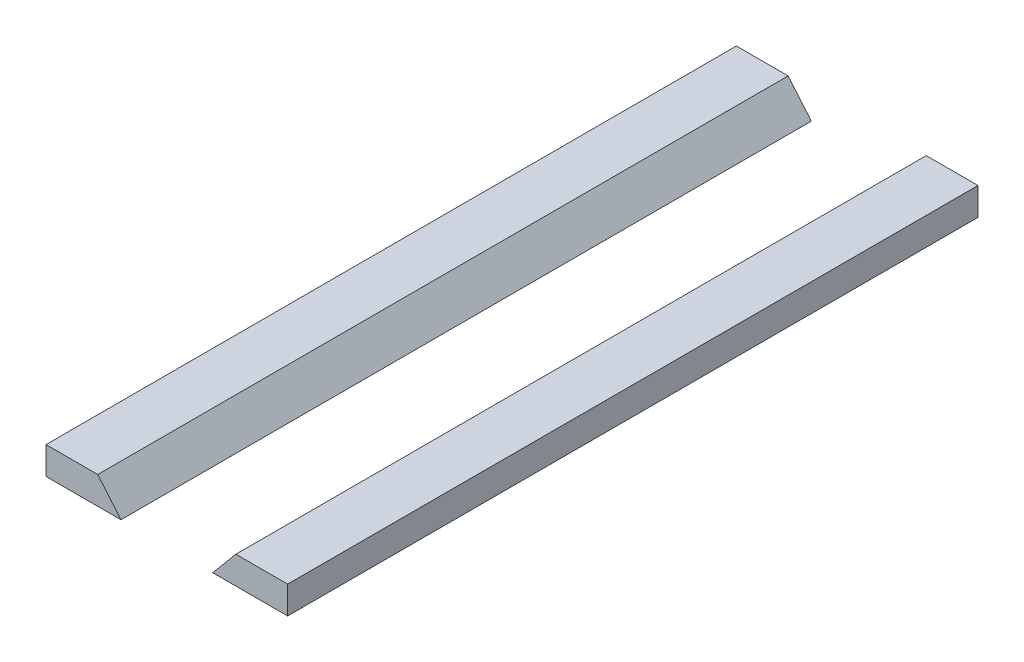
SolidWorks part; units mm, degrees
ref_plane "Płaszczyzna przednia" through (0, 0, 0) normal (0, 0, 1) x (1, 0, 0)
ref_plane "Płaszczyzna górna" through (0, 0, 0) normal (0, 1, 0) x (1, 0, 0)
ref_plane "Płaszczyzna prawa" through (0, 0, 0) normal (1, 0, 0) x (0, 0, -1)
sketch "Szkic1" plane through (0, 0, 0) normal (0, 0, 1) x (1, 0, 0)
  line L0 (-10, 2) -> (-6.6436, -2)
  line L1 (-17.5, 2) -> (17.5, 2)
  line L2 (-17.5, 2) -> (-17.5, -2)
  line L3 (-17.5, -2) -> (17.5, -2)
  line L4 (17.5, 2) -> (17.5, -2)
  line L5 (-17.5, 2) -> (17.5, -2) construction
  line L6 (-17.5, -2) -> (17.5, 2) construction
  line L7 (0, 0) -> (0, 4.7316) construction
  line L8 (10, 2) -> (6.6436, -2)
  point P0 (0, 0)
  dimension "D1" = 4
  dimension "D2" = 50
  dimension "D3" = 20
  dimension "D4" = 35
extrude "Dodanie-wyciągnięcie1" add sketch "Szkic1" against normal blind 100 contours L2 L3 L0 L1 | L1 L8 L3 L4 region at (-12.8598, -0.1219, 0) region at (12.8598, -0.1219, 0)
